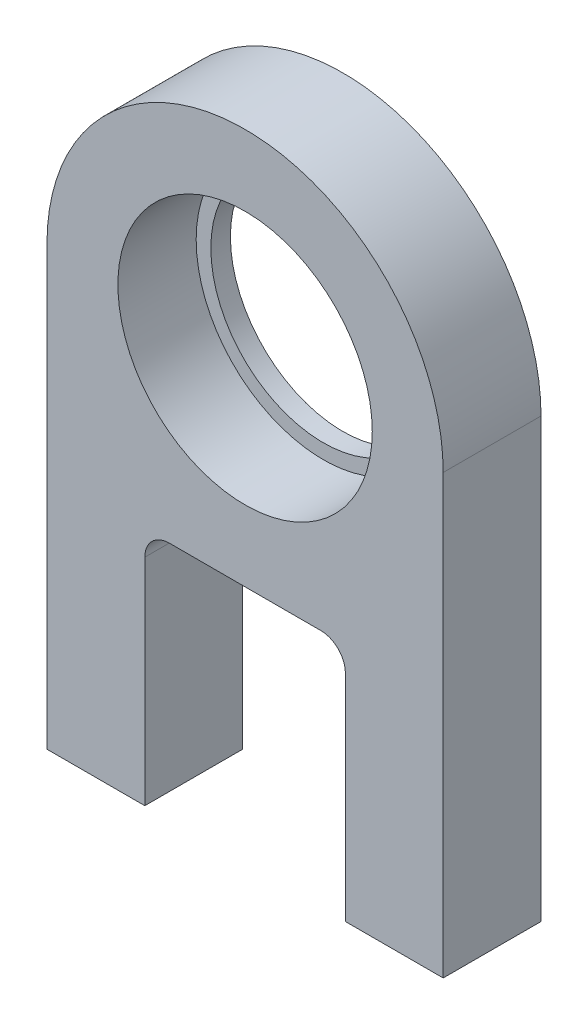
SolidWorks part; units mm, degrees
ref_plane "Front Plane" through (0, 0, 0) normal (0, 0, 1) x (1, 0, 0)
ref_plane "Top Plane" through (0, 0, 0) normal (0, 1, 0) x (1, 0, 0)
ref_plane "Right Plane" through (0, 0, 0) normal (1, 0, 0) x (0, 0, -1)
sketch "Sketch1" plane through (0, 0, 0) normal (0, 0, 1) x (1, 0, 0)
  line L0 (-20.25, 0) -> (-20.25, -44.75)
  line L1 (-20.25, -44.75) -> (-10.25, -44.75)
  line L2 (-10.25, -44.75) -> (10.25, -44.75) construction
  line L3 (10.25, -44.75) -> (20.25, -44.75)
  line L4 (20.25, -44.75) -> (20.25, 0)
  line L5 (-10.25, -44.75) -> (-10.25, -20.25)
  line L6 (-10.25, -20.25) -> (10.25, -20.25)
  line L7 (10.25, -20.25) -> (10.25, -44.75)
  line L8 (0, 20.25) -> (0, -44.75) construction
  circle A0 centre (0, 0) radius 13
  circle A1 centre (0, 0) radius 20.25
  dimension "D1" = 26
  dimension "D2" = 40.5
  dimension "D3" = 10
  dimension "D5" = 65
extrude "Boss-Extrude1" add sketch "Sketch1" along normal blind 5 and the other way blind 5 contours A1 A0 | A1 L6 L7 L3 L4 | A1 L0 L1 L5 L6 region at (-15.376, -28.0674, 0) region at (0, 19.6772, 0) region at (15.376, -28.0674, 0)
sketch "Sketch2" plane through (0, 0, -5) normal (0, 0, -1) x (-1, 0, 0)
  circle A0 centre (0, 0) radius 13
  circle A1 centre (0, 0) radius 11.5
  circle A2 centre (0, 0) radius 13 construction
  dimension "D1" = 23
extrude "Boss-Extrude2" add sketch "Sketch2" against normal blind 2
sketch "Sketch3" plane through (0, -44.75, 0) normal (0, -1, 0) x (1, 0, 0)
  line L0 (10.25, 0) -> (15.75, 0) construction
  line L1 (10.25, -5) -> (10.25, 5) construction
  line L2 (-10.25, 0) -> (-15.75, 0) construction
  line L3 (-10.25, -5) -> (-10.25, 5) construction
  circle A0 centre (-15.75, 0) radius 2.5 construction
  circle A1 centre (15.75, 0) radius 2.5 construction
  dimension "D1" = 5
  dimension "D2" = 5.5
  dimension "D3" = 5.5
hole_wizard "M5x0.8 Tapped Hole1" positions "Sketch4" profile "Sketch5" tap size "M5x0.8" standard "ANSI Metric"
sketch "Sketch4" plane through (0, -44.75, 0) normal (0, -1, 0) x (-1, 0, 0)
  point P0 (15.75, 0)
  point P3 (-15.75, 0)
cosmetic thread "Hole Thread1" parameters "D1"=14.2, "D2"=5
cosmetic thread "Hole Thread2" parameters "D1"=14.2, "D2"=5
sketch "Sketch5" plane through (-15.75, -44.75, 0) normal (1, 0, 0) x (0, 0, -1)
  line L0 (0, 0) -> (0, 16.2618)
  line L1 (0, 16.2618) -> (2.1, 15)
  line L2 (2.1, 15) -> (2.1, 0)
  line L5 (2.1, 0) -> (0, 0)
  line L10 (0, 16.2618) -> (-2.1, 15) construction
  line L11 (0, -6.35) -> (0, 107.95) construction
  dimension "Tap Drill Dia." = 4.2
  dimension "Tap Drill Depth" = 15
  dimension "Drill Angle" = 118
fillet "Fillet1" radius 2.5 2 edges at (10.25, -20.25, 0) (-10.25, -20.25, 0)
